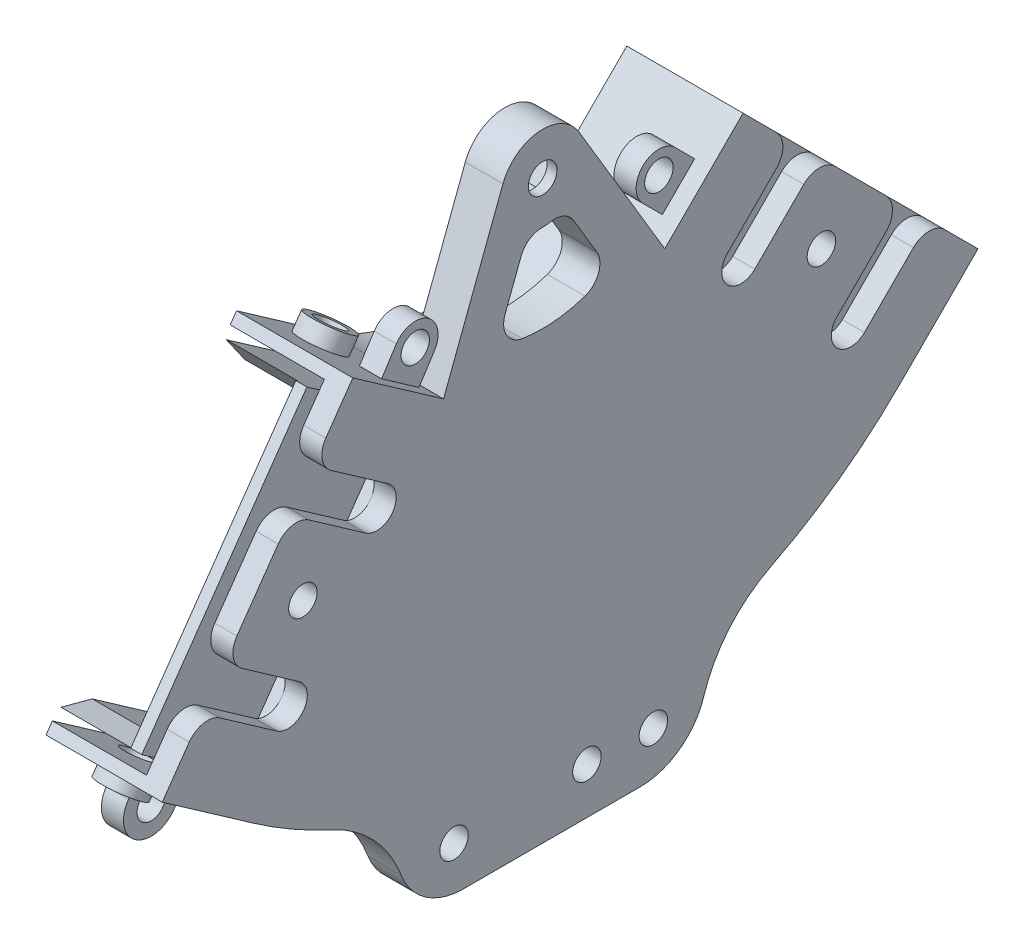
SolidWorks part; units mm, degrees
ref_plane "Front Plane" through (0, 0, 0) normal (0, 0, 1) x (1, 0, 0)
ref_plane "Top Plane" through (0, 0, 0) normal (0, 1, 0) x (1, 0, 0)
ref_plane "Right Plane" through (0, 0, 0) normal (1, 0, 0) x (0, 0, -1)
sketch "Sketch3" plane through (0, 0, 0) normal (1, 0, 0) x (0, 0, -1)
  line L0 (-22.7274, -32.4581) -> (-62.0633, -88.6355)
  line L1 (28.0184, -28.0184) -> (76.5118, -76.5118)
  line L2 (-22.7274, -32.4581) -> (0, 0) construction
  line L3 (0, 0) -> (28.0184, -28.0184) construction
  line L4 (0, 40.513) -> (0, -40.513) construction
  line L5 (-62.0633, -88.6355) -> (-66.4339, -94.8775)
  line L6 (76.5118, -76.5118) -> (81.8999, -81.8999)
  arc A2 (-62.0633, -88.6355) -> (76.5118, -76.5118) centre (0, 0) ccw
  arc A4 (-27.098, -38.7) -> (33.4066, -33.4066) centre (0, 0) ccw
  arc A5 (-22.7274, -32.4581) -> (28.0184, -28.0184) centre (0, 0) ccw
  arc A6 (-66.4339, -94.8775) -> (81.8999, -81.8999) centre (0, 0) ccw
  dimension "D1" = 216.408
  dimension "D2" = 135
  dimension "D3" = 94.488
  dimension "D4" = 7.62
  dimension "D6" = 7.62
  dimension "D5" = 80
extrude "Base extrude" add sketch "Sketch3" along normal blind 58.42 contours L5 A6 L6 A2 | A5 L0 A4 L1 region at (0, -39.9408, -3.4944) region at (0, -109.321, -9.5643)
sketch "Sketch4" plane through (58.42, 0, 0) normal (1, 0, 0) x (0, 0, -1)
  line L0 (-66.4339, -94.8775) -> (-22.7274, -32.4581)
  line L1 (28.0184, -28.0184) -> (81.8999, -81.8999)
  arc A0 (-22.7274, -32.4581) -> (28.0184, -28.0184) centre (0, 0) ccw
  arc A1 (-22.7274, -32.4581) -> (28.0184, -28.0184) centre (0, 0) ccw construction
  arc A2 (-66.4339, -94.8775) -> (81.8999, -81.8999) centre (0, 0) ccw
  arc A3 (-66.4339, -94.8775) -> (81.8999, -81.8999) centre (0, 0) ccw construction
  arc M1 (28.0184, -28.0184) -> (-22.7274, -32.4581) centre (0, 0) cw
  line M2 (-22.7274, -32.4581) -> (-27.098, -38.7)
  arc M3 (-27.098, -38.7) -> (33.4066, -33.4066) centre (0, 0) ccw
  line M4 (33.4066, -33.4066) -> (28.0184, -28.0184)
extrude "Outer wall" add sketch "Sketch4" along normal blind 7.62 contours L0 A2 L1 M3 | M4 M1 M2 M3 region at (58.42, -79.1939, -6.9286) region at (58.42, -39.9408, -3.4944)
ref_plane "Midplane" through (29.21, 0, 0) normal (-1, 0, 0) x (0, 0, 1)
mirror "Mirror1" about plane through (29.21, 0, 0) normal (-1, 0, 0) of "Outer wall"
sketch "Sketch6" plane through (0, 0, 0) normal (0, 0.5736, 0.8192) x (1, 0, 0)
  line L27 (-5.08, -42.164) -> (63.5, -42.164)
  line L28 (-5.08, -42.164) -> (-5.08, -113.284)
  line L29 (-5.08, -113.284) -> (63.5, -113.284)
  line L30 (63.5, -42.164) -> (63.5, -113.284)
  line L31 (-2.54, -44.704) -> (60.96, -44.704)
  line L32 (-2.54, -44.704) -> (-2.54, -110.744)
  line L33 (-2.54, -110.744) -> (60.96, -110.744)
  line L34 (60.96, -44.704) -> (60.96, -110.744)
  line L35 (58.42, -47.244) -> (0, -47.244) construction
  line L36 (0, -108.204) -> (0, -18.7894) construction
  line L37 (58.42, -18.7894) -> (58.42, -108.204) construction
  line L38 (58.42, -108.204) -> (0, -108.204) construction
  line L40 (0, -47.244) -> (58.42, -47.244)
  line L41 (0, -47.244) -> (0, -108.204)
  line L42 (0, -108.204) -> (58.42, -108.204)
  line L43 (58.42, -47.244) -> (58.42, -108.204)
  line L44 (-7.62, -39.624) -> (66.04, -39.624)
  line L45 (-7.62, -39.624) -> (-7.62, -115.824)
  line L46 (-7.62, -115.824) -> (66.04, -115.824)
  line L47 (66.04, -39.624) -> (66.04, -115.824)
  line M21 (-7.62, -39.624) -> (-7.62, -115.824)
  line M22 (-7.62, -115.824) -> (66.04, -115.824)
  line M23 (66.04, -115.824) -> (66.04, -39.624)
  line M24 (66.04, -39.624) -> (-7.62, -39.624)
  line M25 (58.42, -108.204) -> (0, -108.204)
  line M26 (0, -108.204) -> (0, -47.244)
  line M27 (0, -47.244) -> (58.42, -47.244)
  line M28 (58.42, -47.244) -> (58.42, -108.204)
  dimension "D1" = 2.54
  dimension "D2" = 2.54
  dimension "D3" = 2.54
  dimension "D4" = 2.54
  dimension "D5" = 2.54
  dimension "D6" = 2.54
  dimension "D7" = 2.54
  dimension "D8" = 2.54
extrude "Endcap 1" add sketch "Sketch6" along normal blind 25.4 contours L27 L30 L29 L28 M24 M21 M22 M23 | L34 L31 L32 L33 M28 M25 M26 M27 region at (29.21, -37.3698, 26.1667) region at (29.21, -33.3262, 23.3353)
sketch "Sketch7" plane through (0, 0, 0) normal (0, 0.7071, -0.7071) x (1, 0, 0)
  line L0 (-5.08, 113.284) -> (63.5, 113.284)
  line L1 (-5.08, 113.284) -> (-5.08, 42.164)
  line L2 (-5.08, 42.164) -> (63.5, 42.164)
  line L3 (63.5, 113.284) -> (63.5, 42.164)
  line L4 (-2.54, 110.744) -> (60.96, 110.744)
  line L5 (-2.54, 110.744) -> (-2.54, 44.704)
  line L6 (-2.54, 44.704) -> (60.96, 44.704)
  line L7 (60.96, 110.744) -> (60.96, 44.704)
  line L8 (0, 108.204) -> (58.42, 108.204)
  line L9 (0, 108.204) -> (0, 47.244)
  line L10 (0, 47.244) -> (58.42, 47.244)
  line L11 (58.42, 108.204) -> (58.42, 47.244)
  line L12 (-7.62, 115.824) -> (66.04, 115.824)
  line L13 (-7.62, 115.824) -> (-7.62, 39.624)
  line L14 (-7.62, 39.624) -> (66.04, 39.624)
  line L15 (66.04, 115.824) -> (66.04, 39.624)
  line L16 (58.42, 108.204) -> (0, 108.204) construction
  line L17 (58.42, 47.244) -> (58.42, 108.204) construction
  line L18 (66.04, 115.824) -> (-7.62, 115.824) construction
  line L19 (66.04, 39.624) -> (66.04, 115.824) construction
  line L20 (-7.62, 39.624) -> (-7.62, 115.824) construction
  line L21 (66.04, 39.624) -> (-7.62, 39.624) construction
  line M17 (66.04, 115.824) -> (-7.62, 115.824)
  line M18 (-7.62, 115.824) -> (-7.62, 39.624)
  line M19 (-7.62, 39.624) -> (66.04, 39.624)
  line M20 (66.04, 39.624) -> (66.04, 115.824)
  line M21 (0, 47.244) -> (0, 108.204)
  line M22 (0, 108.204) -> (58.42, 108.204)
  line M23 (58.42, 108.204) -> (58.42, 47.244)
  line M24 (58.42, 47.244) -> (0, 47.244)
  dimension "D1" = 2.54
  dimension "D2" = 2.54
  dimension "D3" = 2.54
  dimension "D4" = 2.54
  dimension "D5" = 2.54
  dimension "D6" = 2.54
  dimension "D7" = 2.54
  dimension "D8" = 2.54
extrude "Endcap 2" add sketch "Sketch7" along normal blind 25.4 contours L0 L3 L2 L1 M20 M17 M18 M19 | L7 L4 L5 L6 M24 M21 M22 M23 region at (29.21, -77.66, -77.66) region at (29.21, -81.1505, -81.1505)
chamfer "Internal Chamfer" distance 7.62 angle 20 4 edges at (29.21, -74.0667, 82.8697) (29.21, -24.1312, 47.9045) (29.21, -58.5513, -94.4723) (29.21, -15.446, -51.3671) first distance on face at (29.21, -81.3511, 72.4665) first distance on face at (29.21, -31.4156, 37.5013) first distance on face at (29.21, -67.5315, -85.492) first distance on face at (29.21, -24.4263, -42.3868)
ref_plane "Plane2" through (0, -13.9736, -1.2225) normal (0, -0.9962, -0.0872) x (-1, 0, 0)
sketch "Sketch10" plane through (0, -13.9736, -1.2225) normal (0, -0.9962, -0.0872) x (-1, 0, 0)
  line L0 (-66.04, 93.9078) -> (7.62, 93.9078) construction
  line L1 (-16.51, 95.5358) -> (-41.91, 95.5358)
  line L2 (-16.51, 95.5358) -> (-16.51, -82.1857)
  line L3 (-16.51, -82.1857) -> (-41.91, -82.1857)
  line L4 (-41.91, 95.5358) -> (-41.91, -82.1857)
  point P4 (-29.21, 93.9078)
  point P5 (-29.21, 95.5358)
  dimension "D1" = 25.4
extrude "Flywheel Hole" cut sketch "Sketch10" along normal up to next
sketch "Sketch11" plane through (-7.62, 0, 0) normal (-1, 0, 0) x (0, 0, 1)
  line L0 (-25.2982, 2.2719) -> (-28.0184, -28.0184)
  line L4 (-3.0636, -22.3183) -> (-4.5937, -39.3568)
  line L5 (6.8995, -21.445) -> (11.3704, -37.9575)
  line L6 (-20.4217, -1.79) -> (20.4217, 1.79) construction
  line L7 (24.5172, 6.6383) -> (33.1306, -25.1737)
  line L8 (43.5339, -17.8892) -> (22.7274, -32.4581) construction
  line L10 (1.5525, -17.7121) -> (-2.2178, 25.303) construction
  line L11 (22.7274, -32.4581) -> (43.5339, -17.8892)
  line L12 (22.7274, -32.4581) -> (33.1306, -25.1737)
  arc A1 (-28.0184, -28.0184) -> (22.7274, -32.4581) centre (0, 0) ccw construction
  circle A3 centre (0, 0) radius 4.064
  arc A4 (24.5172, 6.6383) -> (-25.2982, 2.2719) centre (0, 0) ccw
  circle A6 centre (-20.4217, -1.79) radius 2.5
  circle A7 centre (20.4217, 1.79) radius 2.5
  arc A8 (-3.0636, -22.3183) -> (6.8995, -21.445) centre (1.9961, -22.7727) cw
  arc A11 (11.3704, -37.9575) -> (22.7274, -32.4581) centre (0, 0) ccw
  arc A12 (-28.0184, -28.0184) -> (22.7274, -32.4581) centre (0, 0) ccw
  arc A13 (-28.0184, -28.0184) -> (-4.5937, -39.3568) centre (0, 0) ccw
  point P22 (0, 0)
  dimension "D3" = 8.128
  dimension "D2" = 25.4
  dimension "D1" = 5
  dimension "D5" = 5.08
  dimension "D4" = 41
  dimension "D7" = 43.18
  dimension "D6" = 0
extrude "Flywheel holder" add sketch "Sketch11" against normal blind 7.62
sketch "Sketch12" plane through (-7.62, 0, 0) normal (-1, 0, 0) x (0, 0, 1)
  circle A0 centre (0, 0) radius 14.605
  dimension "D1" = 29.21
extrude "Motor insert" cut sketch "Sketch12" against normal blind 6.35
sketch "Sketch14" plane through (-7.62, 0, 0) normal (-1, 0, 0) x (0, 0, 1)
  line L1 (-106.5763, 40.9543) -> (105.556, 40.9543)
  line L2 (-106.5763, 40.9543) -> (-106.5763, -120.0185)
  line L3 (-106.5763, -120.0185) -> (105.556, -120.0185)
  line L4 (105.556, 40.9543) -> (105.556, -120.0185)
extrude "Cut-Extrude2" cut sketch "Sketch14" against normal up to surface (49.53 mm away) up to face at (41.91, -26.9401, -2.3569)
sketch "Sketch15" plane through (41.91, 0, 0) normal (-1, 0, 0) x (0, 0, 1)
  line L0 (-93.8083, -77.7308) -> (-89.6212, -74.1787)
  line L1 (-99.8604, -63.9394) -> (-81.8999, -81.8999) construction
  line L2 (-89.6212, -74.1787) -> (-80.6312, -83.1493)
  line L3 (-80.6312, -83.1493) -> (-85.0539, -86.9012)
  line L4 (-16.51, -121.4959) -> (-16.51, -114.6413)
  line L5 (-16.51, -114.6413) -> (-3.8593, -115.7597)
  line L6 (-3.8593, -115.7597) -> (-3.8593, -120.7059)
  line L7 (63.1155, -104.8839) -> (59.3284, -99.4753)
  line L8 (59.3284, -99.4753) -> (69.9059, -92.4464)
  line L9 (66.4339, -94.8775) -> (87.2404, -80.3086) construction
  line L10 (69.9059, -92.4464) -> (73.4123, -97.454)
  circle A0 centre (-89.7004, -82.5731) radius 3.2639
  circle A1 centre (-10.16, -121.4959) radius 3.2639
  circle A2 centre (68.1904, -101.0671) radius 3.2639
  arc A3 (-93.8083, -77.7308) -> (-85.0539, -86.9012) centre (-89.7004, -82.5731) ccw
  arc A5 (62.868, -104.5305) -> (73.3715, -97.3959) centre (68.1904, -101.0671) ccw
  arc A6 (-81.8999, -81.8999) -> (66.4339, -94.8775) centre (0, 0) ccw construction
  arc A7 (-16.51, -121.4959) -> (-3.8593, -120.7059) centre (-10.16, -121.4959) ccw
  line M28 (-99.8604, -63.9394) -> (-81.8999, -81.8999)
  arc M29 (-81.8999, -81.8999) -> (66.4339, -94.8775) centre (0, 0) ccw
  line M30 (66.4339, -94.8775) -> (87.2404, -80.3086)
  dimension "D4" = 6.5278
  dimension "D5" = 12.7
  dimension "D1" = 121.92
  dimension "D2" = 121.92
  dimension "D3" = 121.92
  dimension "D6" = 10.16
  dimension "D7" = 10.16
  dimension "D8" = 19.05
  dimension "D9" = 12.7
  dimension "D10" = 12.7
  dimension "D11" = 12.7
extrude "Joining screw holes" add sketch "Sketch15" against normal blind 5.08 contours L0 A3 L3 A0 M29 M28 | L4 A7 L6 A1 M29 | L7 A5 L10 A2 M30 M29 region at (41.91, -97.4205, 63.0391) region at (41.91, -115.5565, -10.2161) region at (41.91, -76.1174, -91.5767)
ref_plane "Plane3" through (59.69, 0, 0) normal (1, 0, 0) x (0, 0, -1)
sketch "Sketch16" plane through (59.69, 0, 0) normal (1, 0, 0) x (0, 0, -1)
  line L0 (-43.5339, -17.8892) -> (-22.7274, -32.4581) construction
  line L1 (45.9789, -10.0579) -> (28.0184, -28.0184) construction
  line L2 (-29.7459, -19.9251) -> (-33.1306, -25.1737)
  line L3 (-33.1306, -25.1737) -> (-24.5641, -31.172)
  line L4 (-24.5641, -31.172) -> (-21.1794, -25.9235)
  line L5 (26.7818, -20.2747) -> (31.2719, -24.7649)
  line L6 (31.2719, -24.7649) -> (38.6683, -17.3685)
  line L7 (38.6683, -17.3685) -> (34.1782, -12.8783)
  line L8 (34.1782, -12.8783) -> (26.7818, -20.2747) construction
  circle A0 centre (-25.4, -22.8348) radius 3.2639
  circle A1 centre (30.48, -16.5765) radius 3.2639
  arc A2 (-21.1794, -25.9235) -> (-29.8435, -20.0764) centre (-25.4, -22.8348) ccw
  arc A3 (34.1782, -12.8783) -> (26.7818, -20.2747) centre (30.48, -16.5765) ccw
  dimension "D3" = 6.5278
  dimension "D1" = 6.35
  dimension "D2" = 6.35
  dimension "D4" = 25.4
  dimension "D5" = 30.48
  dimension "D6" = 55.88
  dimension "D7" = 6.2582
extrude "Flywheel cover connectors" add sketch "Sketch16" along normal blind 5.08 contours L4 A2 L2 L3 A0 | L7 L8 A1 L5 L6 | L8 A3 A1 region at (59.69, -18.7043, 22.5078) region at (59.69, -19.2478, -33.1513) region at (59.69, -12.9676, -26.8711)
sketch "Sketch17" plane through (66.04, 0, 0) normal (1, 0, 0) x (0, 0, -1)
  line L0 (-30.48, -111.7415) -> (-30.48, -132.08)
  line L1 (-30.48, -132.08) -> (35.56, -132.08)
  line L2 (35.56, -132.08) -> (35.56, -110.2301)
  circle A0 centre (-20.32, -121.92) radius 3.2639
  circle A1 centre (25.4, -121.92) radius 3.2639
  arc A2 (-66.4339, -94.8775) -> (81.8999, -81.8999) centre (0, 0) ccw construction
  circle A4 centre (10.16, -121.4959) radius 3.2639
  arc A5 (-66.4339, -94.8775) -> (81.8999, -81.8999) centre (0, 0) ccw
  arc A6 (-30.48, -111.7415) -> (35.56, -110.2301) centre (0, 0) ccw
  circle A7 centre (10.16, -121.4959) radius 3.2639 construction
  dimension "D1" = 6.5278
  dimension "D2" = 20.32
  dimension "D3" = 25.4
  dimension "D4" = 121.92
  dimension "D5" = 0
  dimension "D6" = 10.16
  dimension "D7" = 10.16
  dimension "D8" = 10.16
extrude "80-20 connector" add sketch "Sketch17" against normal blind 5.08
fillet "Fillet1" radius 30.48 2 edges at (63.5, -111.7415, 30.48) (63.5, -110.2301, -35.56)
fillet "Fillet2" radius 15.24 2 edges at (63.5, -132.08, -35.56) (63.5, -132.08, 30.48)
sketch "Sketch18" plane through (66.04, 0, 0) normal (1, 0, 0) x (0, 0, -1)
  line L0 (-35.474, -42.9126) -> (-52.6394, -30.8933)
  line L1 (-87.2404, -80.3086) -> (-43.5339, -17.8892) construction
  line L2 (-52.6394, -30.8933) -> (-57.7385, -38.1755)
  line L3 (-57.7385, -38.1755) -> (-40.5731, -50.1948)
  line L4 (-55.8704, -72.0416) -> (-73.0358, -60.0223)
  line L5 (-73.0358, -60.0223) -> (-78.1349, -67.3046)
  line L6 (-78.1349, -67.3046) -> (-60.9695, -79.3239)
  line L7 (42.3868, -36.1006) -> (57.2042, -21.2832)
  line L8 (45.9789, -10.0579) -> (99.8604, -63.9394) construction
  line L9 (57.2042, -21.2832) -> (63.4904, -27.5694)
  line L10 (63.4904, -27.5694) -> (48.673, -42.3868)
  line L11 (67.5315, -61.2453) -> (82.3489, -46.4279)
  line L12 (82.3489, -46.4279) -> (88.6351, -52.7141)
  line L13 (88.6351, -52.7141) -> (73.8177, -67.5315)
  line L14 (-43.5339, -17.8892) -> (-22.7274, -32.4581) construction
  line L15 (45.9789, -10.0579) -> (28.0184, -28.0184) construction
  line L16 (99.8604, -63.9394) -> (81.8999, -81.8999) construction
  line L17 (-87.2404, -80.3086) -> (-66.4339, -94.8775) construction
  line L18 (-24.1843, -34.5387) -> (-64.977, -92.7968) construction
  arc A0 (-40.5731, -50.1948) -> (-35.474, -42.9126) centre (-38.0236, -46.5537) ccw
  arc A1 (-60.9695, -79.3239) -> (-55.8704, -72.0416) centre (-58.42, -75.6827) ccw
  arc A2 (42.3868, -36.1006) -> (48.673, -42.3868) centre (45.5299, -39.2437) ccw
  arc A3 (67.5315, -61.2453) -> (73.8177, -67.5315) centre (70.6746, -64.3884) ccw
  dimension "D1" = 8.89
  dimension "D3" = 20.32
  dimension "D4" = 20.32
  dimension "D5" = 20.32
  dimension "D6" = 20.32
extrude "Support Removal" cut sketch "Sketch18" against normal up to next
fillet "Fillet3" radius 5.08 8 edges at (64.77, -52.7141, -88.6351) (64.77, -46.4279, -82.3489) (64.77, -27.5694, -63.4904) (64.77, -21.2832, -57.2042) (64.77, -67.3046, 78.1349) (64.77, -60.0223, 73.0358) (64.77, -38.1755, 57.7385) (64.77, -30.8933, 52.6394)
sketch "Sketch19" plane through (66.04, 0, 0) normal (1, 0, 0) x (0, 0, -1)
  line L0 (-70.122, -55.861) -> (-60.6522, -42.3368) construction
  line L1 (67.0825, -31.1615) -> (78.7568, -42.8358) construction
  line L2 (-65.3871, -49.0989) -> (-54.9839, -56.3834) construction
  line L3 (-34.3825, -49.1033) -> (-54.7788, -78.2323) construction
  line L4 (67.5315, -67.5315) -> (42.3868, -42.3868) construction
  line L5 (72.9197, -36.9987) -> (63.9394, -45.9789) construction
  circle A0 centre (-54.9839, -56.3834) radius 3.2639
  circle A1 centre (63.9394, -45.9789) radius 3.2639
  point P4 (-65.3871, -49.0989)
  point P5 (72.9197, -36.9987)
  dimension "D1" = 6.5278
  dimension "D2" = 12.7
  dimension "D3" = 12.7
extrude "Cut-Extrude3" cut sketch "Sketch19" against normal up to next contours A1 | A0 region at (66.04, -56.3834, 54.9839) region at (66.04, -45.9789, -63.9394)
sketch "Sketch20" plane through (0, -94.8775, 66.4339) normal (0, -0.8192, 0.5736) x (1, 0, 0)
  line L0 (63.5, 25.4) -> (63.5, 0) construction
  line L1 (41.91, 0) -> (63.5, 0) construction
  circle A0 centre (50.8, 12.7) radius 3.2639
  dimension "D1" = 6.5278
  dimension "D2" = 12.7
  dimension "D3" = 12.7
extrude "Cut-Extrude4" cut sketch "Sketch20" against normal up to next
ref_plane "Plane4" through (0, -63.6678, 44.5807) normal (0, 0.8192, -0.5736) x (1, 0, 0)
mirror "Mirror2" about plane through (0, -63.6678, 44.5807) normal (0, 0.8192, -0.5736) of "Cut-Extrude4"
sketch "Sketch21" plane through (0, -81.8999, -81.8999) normal (0, -0.7071, -0.7071) x (1, 0, 0)
  line L0 (66.04, 0) -> (46.99, 0) construction
  line L1 (63.5, -25.4) -> (63.5, 0) construction
  circle A0 centre (50.8, -12.7) radius 3.2639
  dimension "D1" = 6.5278
  dimension "D2" = 12.7
  dimension "D3" = 12.7
extrude "Cut-Extrude5" cut sketch "Sketch21" against normal up to next contours A0
sketch "Sketch22" plane through (66.04, 0, 0) normal (1, 0, 0) x (0, 0, -1)
  line L38 (99.8604, -63.9394) -> (92.2272, -56.3062)
  line L39 (85.043, -56.3062) -> (73.8177, -67.5315)
  line L40 (67.5315, -61.2453) -> (78.7568, -50.02)
  line L41 (78.7568, -42.8358) -> (67.0825, -31.1615)
  line L42 (59.8983, -31.1615) -> (48.673, -42.3868)
  line L43 (42.3868, -36.1006) -> (53.6121, -24.8753)
  line L44 (53.6121, -17.6911) -> (45.9789, -10.0579)
  line L45 (45.9789, -10.0579) -> (28.0184, -28.0184)
  line L46 (-22.7274, -32.4581) -> (-43.5339, -17.8892)
  line L47 (-43.5339, -17.8892) -> (-49.7256, -26.732)
  line L48 (-48.4781, -33.807) -> (-35.474, -42.9126)
  line L49 (-40.5731, -50.1948) -> (-53.5772, -41.0893)
  line L50 (-60.6522, -42.3368) -> (-70.122, -55.861)
  line L51 (-68.8745, -62.9361) -> (-55.8704, -72.0416)
  line L52 (-60.9695, -79.3239) -> (-73.9736, -70.2184)
  line L53 (-81.0486, -71.4659) -> (-87.2404, -80.3086)
  line L54 (-87.2404, -80.3086) -> (-66.4339, -94.8775)
  line L55 (-18.1792, -132.08) -> (22.4243, -132.08)
  line L56 (81.8999, -81.8999) -> (99.8604, -63.9394)
  line L57 (99.8604, -63.9394) -> (92.2272, -56.3062)
  line L58 (85.043, -56.3062) -> (73.8177, -67.5315)
  line L59 (67.5315, -61.2453) -> (78.7568, -50.02)
  line L60 (78.7568, -42.8358) -> (67.0825, -31.1615)
  line L61 (59.8983, -31.1615) -> (48.673, -42.3868)
  line L62 (42.3868, -36.1006) -> (53.6121, -24.8753)
  line L63 (53.6121, -17.6911) -> (45.9789, -10.0579)
  line L64 (45.9789, -10.0579) -> (28.0184, -28.0184)
  line L65 (-22.7274, -32.4581) -> (-43.5339, -17.8892)
  line L66 (-43.5339, -17.8892) -> (-49.7256, -26.732)
  line L67 (-48.4781, -33.807) -> (-35.474, -42.9126)
  line L68 (-40.5731, -50.1948) -> (-53.5772, -41.0893)
  line L69 (-60.6522, -42.3368) -> (-70.122, -55.861)
  line L70 (-68.8745, -62.9361) -> (-55.8704, -72.0416)
  line L71 (-60.9695, -79.3239) -> (-73.9736, -70.2184)
  line L72 (-81.0486, -71.4659) -> (-87.2404, -80.3086)
  line L73 (-87.2404, -80.3086) -> (-66.4339, -94.8775)
  line L74 (-18.1792, -132.08) -> (22.4243, -132.08)
  line L75 (81.8999, -81.8999) -> (99.8604, -63.9394)
  circle A21 centre (-54.9839, -56.3834) radius 3.2639
  circle A22 centre (-54.9839, -56.3834) radius 3.2639
  circle A24 centre (-20.32, -121.92) radius 3.2639
  circle A25 centre (-20.32, -121.92) radius 3.2639
  circle A27 centre (10.16, -121.4959) radius 3.2639
  circle A28 centre (10.16, -121.4959) radius 3.2639
  circle A30 centre (25.4, -121.92) radius 3.2639
  circle A31 centre (25.4, -121.92) radius 3.2639
  circle A33 centre (63.9394, -45.9789) radius 3.2639
  circle A34 centre (63.9394, -45.9789) radius 3.2639
  arc A38 (92.2272, -56.3062) -> (85.043, -56.3062) centre (88.6351, -59.8983) ccw
  arc A39 (67.5315, -61.2453) -> (73.8177, -67.5315) centre (70.6746, -64.3884) ccw
  arc A40 (78.7568, -50.02) -> (78.7568, -42.8358) centre (75.1647, -46.4279) ccw
  arc A41 (67.0825, -31.1615) -> (59.8983, -31.1615) centre (63.4904, -34.7536) ccw
  arc A42 (42.3868, -36.1006) -> (48.673, -42.3868) centre (45.5299, -39.2437) ccw
  arc A43 (53.6121, -24.8753) -> (53.6121, -17.6911) centre (50.02, -21.2832) ccw
  arc A44 (-22.7274, -32.4581) -> (28.0184, -28.0184) centre (0, 0) ccw
  arc A45 (-49.7256, -26.732) -> (-48.4781, -33.807) centre (-45.5643, -29.6458) ccw
  arc A46 (-40.5731, -50.1948) -> (-35.474, -42.9126) centre (-38.0236, -46.5537) ccw
  arc A47 (-53.5772, -41.0893) -> (-60.6522, -42.3368) centre (-56.491, -45.2506) ccw
  arc A48 (-70.122, -55.861) -> (-68.8745, -62.9361) centre (-65.9607, -58.7748) ccw
  arc A49 (-60.9695, -79.3239) -> (-55.8704, -72.0416) centre (-58.42, -75.6827) ccw
  arc A50 (-73.9736, -70.2184) -> (-81.0486, -71.4659) centre (-76.8873, -74.3796) ccw
  arc A51 (-66.4339, -94.8775) -> (-48.2489, -105.296) centre (0, 0) ccw
  arc A52 (-32.4348, -122.2285) -> (-48.2489, -105.296) centre (-60.9459, -133.0055) ccw
  arc A53 (-32.4348, -122.2285) -> (-18.1792, -132.08) centre (-18.1792, -116.84) ccw
  arc A54 (22.4243, -132.08) -> (36.9629, -121.4104) centre (22.4243, -116.84) ccw
  arc A55 (52.2817, -103.3529) -> (36.9629, -121.4104) centre (66.04, -130.5511) ccw
  arc A56 (52.2817, -103.3529) -> (81.8999, -81.8999) centre (0, 0) ccw
  arc A57 (92.2272, -56.3062) -> (85.043, -56.3062) centre (88.6351, -59.8983) ccw
  arc A58 (67.5315, -61.2453) -> (73.8177, -67.5315) centre (70.6746, -64.3884) ccw
  arc A59 (78.7568, -50.02) -> (78.7568, -42.8358) centre (75.1647, -46.4279) ccw
  arc A60 (67.0825, -31.1615) -> (59.8983, -31.1615) centre (63.4904, -34.7536) ccw
  arc A61 (42.3868, -36.1006) -> (48.673, -42.3868) centre (45.5299, -39.2437) ccw
  arc A62 (53.6121, -24.8753) -> (53.6121, -17.6911) centre (50.02, -21.2832) ccw
  arc A63 (-22.7274, -32.4581) -> (28.0184, -28.0184) centre (0, 0) ccw
  arc A64 (-49.7256, -26.732) -> (-48.4781, -33.807) centre (-45.5643, -29.6458) ccw
  arc A65 (-40.5731, -50.1948) -> (-35.474, -42.9126) centre (-38.0236, -46.5537) ccw
  arc A66 (-53.5772, -41.0893) -> (-60.6522, -42.3368) centre (-56.491, -45.2506) ccw
  arc A67 (-70.122, -55.861) -> (-68.8745, -62.9361) centre (-65.9607, -58.7748) ccw
  arc A68 (-60.9695, -79.3239) -> (-55.8704, -72.0416) centre (-58.42, -75.6827) ccw
  arc A69 (-73.9736, -70.2184) -> (-81.0486, -71.4659) centre (-76.8873, -74.3796) ccw
  arc A70 (-66.4339, -94.8775) -> (-48.2489, -105.296) centre (0, 0) ccw
  arc A71 (-32.4348, -122.2285) -> (-48.2489, -105.296) centre (-60.9459, -133.0055) ccw
  arc A72 (-32.4348, -122.2285) -> (-18.1792, -132.08) centre (-18.1792, -116.84) ccw
  arc A73 (22.4243, -132.08) -> (36.9629, -121.4104) centre (22.4243, -116.84) ccw
  arc A74 (52.2817, -103.3529) -> (36.9629, -121.4104) centre (66.04, -130.5511) ccw
  arc A75 (52.2817, -103.3529) -> (81.8999, -81.8999) centre (0, 0) ccw
  circle M44 centre (63.9394, -45.9789) radius 3.2639
  circle M45 centre (-54.9839, -56.3834) radius 3.2639
  line M46 (99.8604, -63.9394) -> (92.2272, -56.3062)
  arc M47 (92.2272, -56.3062) -> (85.043, -56.3062) centre (88.6351, -59.8983) ccw
  line M48 (85.043, -56.3062) -> (73.8177, -67.5315)
  arc M49 (73.8177, -67.5315) -> (67.5315, -61.2453) centre (70.6746, -64.3884) cw
  line M50 (67.5315, -61.2453) -> (78.7568, -50.02)
  arc M51 (78.7568, -50.02) -> (78.7568, -42.8358) centre (75.1647, -46.4279) ccw
  line M52 (78.7568, -42.8358) -> (67.0825, -31.1615)
  arc M53 (67.0825, -31.1615) -> (59.8983, -31.1615) centre (63.4904, -34.7536) ccw
  line M54 (59.8983, -31.1615) -> (48.673, -42.3868)
  arc M55 (48.673, -42.3868) -> (42.3868, -36.1006) centre (45.5299, -39.2437) cw
  line M56 (42.3868, -36.1006) -> (53.6121, -24.8753)
  arc M57 (53.6121, -24.8753) -> (53.6121, -17.6911) centre (50.02, -21.2832) ccw
  line M58 (53.6121, -17.6911) -> (45.9789, -10.0579)
  line M59 (45.9789, -10.0579) -> (28.0184, -28.0184)
  arc M60 (28.0184, -28.0184) -> (-22.7274, -32.4581) centre (0, 0) cw
  line M61 (-22.7274, -32.4581) -> (-43.5339, -17.8892)
  line M62 (-43.5339, -17.8892) -> (-49.7256, -26.732)
  arc M63 (-49.7256, -26.732) -> (-48.4781, -33.807) centre (-45.5643, -29.6458) ccw
  line M64 (-48.4781, -33.807) -> (-35.474, -42.9126)
  arc M65 (-35.474, -42.9126) -> (-40.5731, -50.1948) centre (-38.0236, -46.5537) cw
  line M66 (-40.5731, -50.1948) -> (-53.5772, -41.0893)
  arc M67 (-53.5772, -41.0893) -> (-60.6522, -42.3368) centre (-56.491, -45.2506) ccw
  line M68 (-60.6522, -42.3368) -> (-70.122, -55.861)
  arc M69 (-70.122, -55.861) -> (-68.8745, -62.9361) centre (-65.9607, -58.7748) ccw
  line M70 (-68.8745, -62.9361) -> (-55.8704, -72.0416)
  arc M71 (-55.8704, -72.0416) -> (-60.9695, -79.3239) centre (-58.42, -75.6827) cw
  line M72 (-60.9695, -79.3239) -> (-73.9736, -70.2184)
  arc M73 (-73.9736, -70.2184) -> (-81.0486, -71.4659) centre (-76.8873, -74.3796) ccw
  line M74 (-81.0486, -71.4659) -> (-87.2404, -80.3086)
  line M75 (-87.2404, -80.3086) -> (-66.4339, -94.8775)
  arc M76 (-66.4339, -94.8775) -> (-48.2489, -105.296) centre (0, 0) ccw
  arc M77 (-48.2489, -105.296) -> (-32.4348, -122.2285) centre (-60.9459, -133.0055) cw
  arc M78 (-32.4348, -122.2285) -> (-18.1792, -132.08) centre (-18.1792, -116.84) ccw
  line M79 (-18.1792, -132.08) -> (22.4243, -132.08)
  arc M80 (22.4243, -132.08) -> (36.9629, -121.4104) centre (22.4243, -116.84) ccw
  arc M81 (36.9629, -121.4104) -> (52.2817, -103.3529) centre (66.04, -130.5511) cw
  arc M82 (52.2817, -103.3529) -> (81.8999, -81.8999) centre (0, 0) ccw
  line M83 (81.8999, -81.8999) -> (99.8604, -63.9394)
  circle M84 centre (10.16, -121.4959) radius 3.2639
  circle M85 centre (25.4, -121.92) radius 3.2639
  circle M86 centre (-20.32, -121.92) radius 3.2639
  dimension "D1" = 0
  dimension "D2" = 0
  dimension "D3" = 0
  dimension "D4" = 0
  dimension "D5" = 0
  dimension "D6" = 0
extrude "Thicken" add sketch "Sketch22" along normal blind 2.54 contours M83 M46 M47 M48 M49 M50 M51 M52 M53 M54 M55 M56 M57 M58 M59 M60 M61 M62 M63 M64 M65 M66 M67 M68 M69 M70 M71 M72 M73 M74 M75 M76 M77 M78 M79 M80 M81 M82 M45 M84 M86 M85 M44 region at (66.04, -75.2354, -5.8008)
sketch "Sketch23" plane through (68.58, 0, 0) normal (1, 0, 0) x (0, 0, -1)
  line L0 (-9.1013, 3.4534) -> (-22.7274, -32.4581)
  line L3 (8.3634, 4.9813) -> (28.0184, -28.0184)
  line L5 (-3.4534, -9.1013) -> (-10.6035, -27.9455)
  line L6 (28.0184, -28.0184) -> (45.9789, -10.0579)
  line L8 (15.2951, -25.6796) -> (15.2951, -25.6796)
  line L10 (0, 0) -> (-10.6035, -27.9455) construction
  line L11 (0, 0) -> (15.2951, -25.6796) construction
  line L12 (4.9813, -8.3634) -> (15.2951, -25.6796)
  line L19 (28.0184, -28.0184) -> (28.1487, -28.2372) construction
  line L20 (8.3634, 4.9813) -> (28.1487, -28.2372) construction
  circle A0 centre (0, 0) radius 3.302
  arc A1 (8.3634, 4.9813) -> (-9.1013, 3.4534) centre (0, 0) ccw
  arc A4 (-10.6035, -27.9455) -> (15.2951, -25.6796) centre (0, 0) ccw
  arc A5 (-22.7274, -32.4581) -> (28.0184, -28.0184) centre (0, 0) ccw
  arc A6 (-22.7274, -32.4581) -> (28.0184, -28.0184) centre (0, 0) ccw
  arc A7 (0, 0) -> (0, 0) centre (0, 0) ccw
  arc A8 (-3.4534, -9.1013) -> (4.9813, -8.3634) centre (0, 0) ccw
  arc A9 (8.3634, 4.9813) -> (-9.1013, 3.4534) centre (0, 0) ccw
  line M29 (45.9789, -10.0579) -> (28.0184, -28.0184)
  arc M30 (28.0184, -28.0184) -> (-22.7274, -32.4581) centre (0, 0) cw
  dimension "D2" = 0
extrude "Axle Holder" add sketch "Sketch23" against normal blind 8.636 contours A1 L0 A0 L5 A8 L12 A4 M30 M29 region at (68.58, 8.9922, 0.7867)
fillet "Fillet4" radius 5.08 4 edges at (64.262, -8.3634, -4.9813) (64.262, -9.1013, 3.4534) (64.262, -25.6796, -15.2951) (64.262, -27.9455, 10.6035)
sketch "Sketch24" plane through (59.944, 0, 0) normal (-1, 0, 0) x (0, 0, 1)
  line L6 (-3.4462, 5.969) -> (3.4462, 5.969)
  line L7 (3.4462, 5.969) -> (6.8924, 0)
  line L8 (6.8924, 0) -> (3.4462, -5.969)
  line L9 (3.4462, -5.969) -> (-3.4462, -5.969)
  line L10 (-3.4462, -5.969) -> (-6.8924, 0)
  line L11 (-6.8924, 0) -> (-3.4462, 5.969)
  line L12 (-3.4462, 5.969) -> (3.4462, -5.969) construction
  point P2 (0, 0)
  dimension "D1" = 120
  dimension "D2" = 11.938
extrude "Nut hole" cut sketch "Sketch24" against normal blind 6.35
sketch "Sketch25" plane through (0, -32.4581, 22.7274) normal (0, 0.8192, -0.5736) x (1, 0, 0)
  circle A0 centre (50.8, -12.7) radius 3.2639
  circle A1 centre (50.8, -12.7) radius 5.08
  circle A2 centre (50.8, -12.7) radius 3.2639 construction
  dimension "D1" = 10.16
extrude "Boss-Extrude1" add sketch "Sketch25" along normal blind 3.81
sketch "Sketch26" plane through (0, -94.8775, 66.4339) normal (0, -0.8192, 0.5736) x (1, 0, 0)
  circle A0 centre (50.8, 12.7) radius 3.2639
  circle A1 centre (50.8, 12.7) radius 5.08
  circle A2 centre (50.8, 12.7) radius 3.2639 construction
  dimension "D1" = 10.16
extrude "Boss-Extrude2" add sketch "Sketch26" along normal blind 3.81
